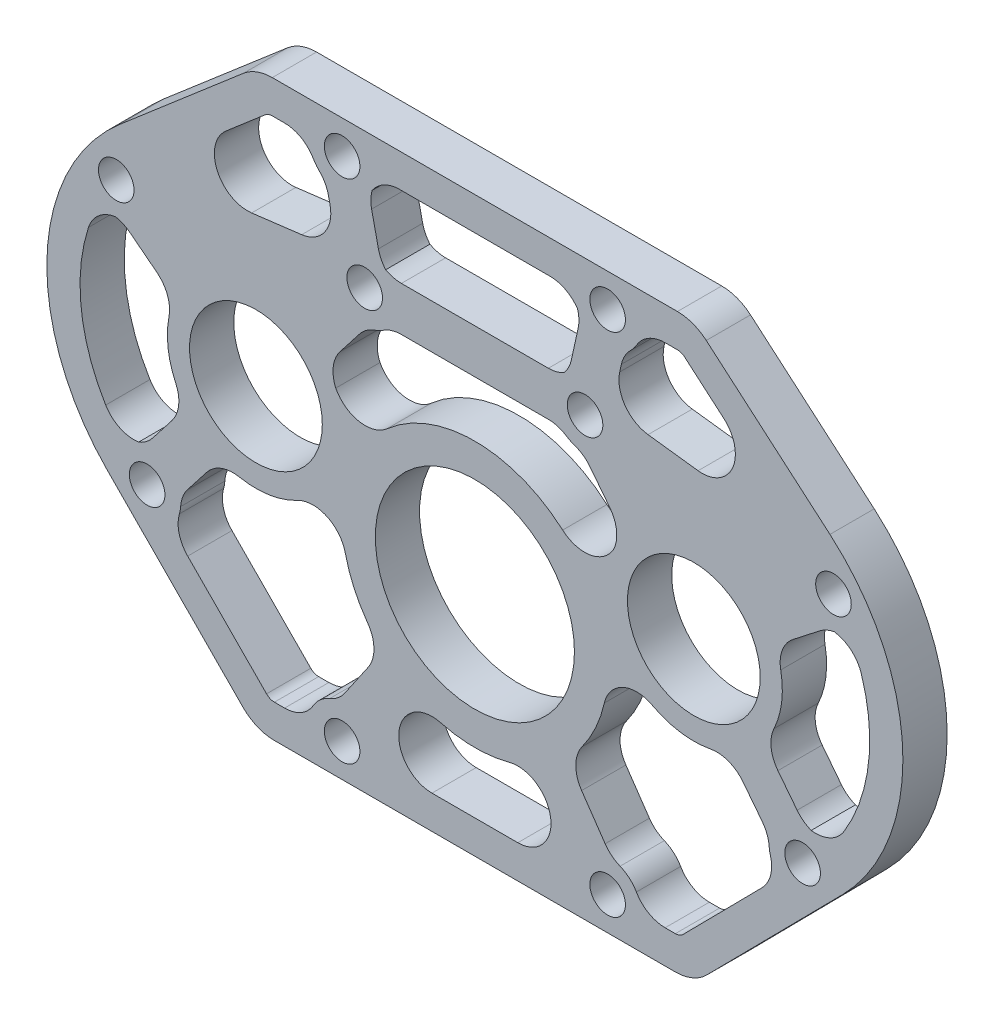
SolidWorks part; units mm, degrees
material "6061-T6 (SS)"
ref_plane "Front Plane" through (0, 0, 0) normal (0, 0, 1) x (1, 0, 0)
ref_plane "Top Plane" through (0, 0, 0) normal (0, 1, 0) x (1, 0, 0)
ref_plane "Right Plane" through (0, 0, 0) normal (1, 0, 0) x (0, 0, -1)
sketch "Sketch1" plane through (0, 0, 0) normal (0, 0, 1) x (1, 0, 0)
  line L0 (127, 25.4) -> (127, 0) construction
  line L1 (0, 0) -> (254, 0)
  line L2 (0, 0) -> (0, 25.4)
  line L3 (0, 25.4) -> (254, 25.4)
  line L4 (254, 0) -> (254, 25.4)
  line L18 (110.6338, 19.05) -> (106.9677, 12.7)
  line L19 (106.9677, 12.7) -> (110.6338, 6.35)
  line L20 (110.6338, 6.35) -> (117.9662, 6.35)
  line L21 (117.9662, 6.35) -> (121.6323, 12.7)
  line L22 (121.6323, 12.7) -> (117.9662, 19.05)
  line L23 (117.9662, 19.05) -> (110.6338, 19.05)
  circle A0 centre (82.8819, 22.86) radius 30 construction
  circle A1 centre (145.7181, 22.86) radius 30 construction
  circle A2 centre (82.8819, 22.86) radius 7.62 construction
  circle A3 centre (145.7181, 22.86) radius 8.636
  circle A4 centre (82.8819, 22.86) radius 8.636
  circle A5 centre (145.7181, 22.86) radius 7.62 construction
  circle A6 centre (114.3, 12.7) radius 25.4 construction
  circle A7 centre (114.3, 12.7) radius 26.67
  circle A8 centre (114.3, 12.7) radius 22.2377 construction
  circle A11 centre (114.3, 12.7) radius 6.35 construction
  dimension "D4" = 17.272
  dimension "D9" = 53.34
  dimension "D13" = 12.7
  dimension "D1" = 25.4
  dimension "D2" = 254
  dimension "D10" = 12.7
  dimension "D12" = 12.7
  dimension "D14" = 10.16
sketch "Sketch3" plane through (0, 0, 0) normal (0, 0, 1) x (1, 0, 0)
  line L0 (82.8819, 52.86) -> (145.7181, 52.86) construction
  line L5 (82.8819, -7.14) -> (145.7181, -7.14) construction
  line L6 (82.8819, 22.86) -> (98.4918, 42.8972) construction
  line L9 (114.3, 52.86) -> (114.3, -19.84) construction
  line L10 (63.3497, 45.6304) -> (82.8819, 62.385)
  line L25 (82.8819, 62.385) -> (145.7181, 62.385)
  line L26 (145.7181, 62.385) -> (165.2503, 45.6304)
  line L27 (110.6338, 19.05) -> (106.9677, 12.7)
  line L28 (106.9677, 12.7) -> (110.6338, 6.35)
  line L29 (110.6338, 6.35) -> (117.9662, 6.35)
  line L30 (117.9662, 6.35) -> (121.6323, 12.7)
  line L31 (121.6323, 12.7) -> (117.9662, 19.05)
  line L32 (117.9662, 19.05) -> (110.6338, 19.05)
  line L33 (110.565, 18.9308) -> (106.9677, 12.7)
  line L34 (106.9677, 12.7) -> (110.6338, 6.35)
  line L35 (110.6338, 6.35) -> (117.9662, 6.35)
  line L36 (117.9662, 6.35) -> (121.6323, 12.7)
  line L37 (121.6323, 12.7) -> (117.9662, 19.05)
  line L38 (117.9662, 19.05) -> (110.6338, 19.05)
  line L39 (96.3395, 30.6605) -> (132.2605, -5.2605) construction
  line L40 (82.8819, 22.86) -> (114.3, 12.7) construction
  line L41 (95.25, 57.6225) -> (133.35, 57.6225) construction
  line L43 (95.25, -15.0775) -> (133.35, -15.0775) construction
  line L44 (145.7181, -19.84) -> (167.0663, 1.7827)
  line L45 (82.8819, -19.84) -> (145.7181, -19.84)
  line L46 (61.5337, 1.7827) -> (82.8819, -19.84)
  line L47 (82.8819, 22.86) -> (67.272, 2.8228) construction
  line L48 (82.8819, 22.86) -> (67.272, 2.8228) construction
  line L49 (82.8819, 22.86) -> (62.8447, 38.4699) construction
  circle A2 centre (82.8819, 22.86) radius 30 construction
  circle A9 centre (114.3, 12.7) radius 26.67
  circle A10 centre (114.3, 12.7) radius 26.67 construction
  circle A11 centre (82.8819, 22.86) radius 8.636
  circle A12 centre (82.8819, 22.86) radius 8.636 construction
  circle A13 centre (145.7181, 22.86) radius 8.636
  circle A16 centre (145.7181, 22.86) radius 8.636 construction
  circle A17 centre (95.25, 57.6225) radius 2.5527
  circle A19 centre (114.3, 12.7) radius 25.4 construction
  circle A20 centre (114.3, 12.7) radius 22.2377 construction
  circle A22 centre (114.3, 12.7) radius 25.4 construction
  circle A23 centre (114.3, 12.7) radius 22.2377 construction
  arc A24 (112.6104, 26.8872) -> (104.6233, 2.1884) centre (82.8819, 22.86) ccw
  circle A25 centre (114.3, 12.7) radius 14.2875
  circle A26 centre (82.8819, 22.86) radius 9.525
  circle A27 centre (145.7181, 22.86) radius 9.525
  circle A37 centre (133.35, 57.6225) radius 2.5527
  circle A38 centre (133.35, -15.0775) radius 2.5527
  circle A39 centre (95.25, -15.0775) radius 2.5527
  circle A40 centre (67.272, 2.8228) radius 2.5527
  circle A41 centre (62.8447, 38.4699) radius 2.5527
  circle A42 centre (98.4918, 42.8972) radius 2.5527
  circle A43 centre (161.328, 2.8228) radius 2.5527
  circle A44 centre (165.7553, 38.4699) radius 2.5527
  circle A45 centre (130.1082, 42.8972) radius 2.5527
  circle A46 centre (95.25, -15.0775) radius 4.7625 construction
  arc A47 (123.9767, 2.1884) -> (115.9896, 26.8872) centre (145.7181, 22.86) ccw
  circle A48 centre (133.35, -15.0775) radius 4.7625 construction
  circle A49 centre (95.25, 57.6225) radius 4.7625 construction
  circle A50 centre (133.35, 57.6225) radius 4.7625 construction
  point P2 (114.3, 52.86)
  point P31 (114.3, -19.84)
  point P41 (114.3, 62.385)
  point P59 (114.3, 57.6225)
  point P60 (114.3, -15.0775)
  point P69 (114.3, 12.7)
  point P78 (82.8819, 22.86)
  point P84 (114.3, -22.0625)
  dimension "D3" = 70
  dimension "D4" = 9.525
  dimension "D2" = 45
  dimension "D8" = 25.4
  dimension "D14" = 28.575
  dimension "D15" = 19.05
  dimension "D16" = 3
  dimension "D5" = 5.1054
  dimension "D12" = 5.1054
  dimension "D7" = 4.7625
  dimension "D17" = 90
  dimension "2" = 50.8
  dimension "D6" = 19.05
  dimension "D18" = 7.9375
  dimension "D9" = 0
  dimension "D10" = 0
  dimension "D11" = 0
  dimension "D13" = 0
extrude "Boss-Extrude1" add sketch "Sketch3" along normal blind 6.35 contours A24 A10 L26 L25 L10 A37 A17 | A24 L46 L45 L44 A10 A38 A39 | A10 A24 A12 A40 A42 | A23 A24 A25 | A23 A22 A12 | A22 A24 A10 A12 | A22 A12 A10 A24 | A24 A22 A23 | A24 A10 A22 | A22 A24 A23 | A25 A24 A23 | A25 A23 A24 | A24 A23 A22 | A24 A22 A10 | A23 A24 A22 | A23 A45 A25 A44 | A22 A45 A23 A44 A16 | A23 A45 A22 | A22 A45 A16 A10 | A10 A16 A43 | A22 A44 A23 | A22 A44 A10 A16 | A10 A26 A12 | A22 A12 A10 | A12 A22 | A10 A27 A16 | A16 A22 | A22 A16 A10 region at (87.3231, 51.7029, 0) region at (114.3, 53.784, 0) region at (76.6658, -7.5892, 0) region at (98.4388, 17.8292, 0) region at (114.3, 34.3639, 0) region at (114.3, -6.358, 0) region at (141.2769, 51.7029, 0) region at (130.1612, 17.8292, 0)
fillet "Fillet1" radius 6.35 4 edges at (145.7181, -19.84, 3.175) (82.8819, -19.84, 3.175) (145.7181, 62.385, 3.175) (82.8819, 62.385, 3.175)
sketch "Sketch4" plane through (0, 0, 6.35) normal (0, 0, 1) x (1, 0, 0)
  line L0 (85.536, -15.0775) -> (143.064, -15.0775)
  line L1 (144.1937, -14.6053) -> (163.6773, 5.1287)
  line L2 (162.1496, 42.0156) -> (144.4013, 57.2399)
  line L3 (143.3677, 57.6225) -> (85.2323, 57.6225)
  line L4 (84.1987, 57.2399) -> (66.4504, 42.0156)
  line L5 (64.9227, 5.1287) -> (84.4063, -14.6053)
  line L6 (85.536, -19.84) -> (143.064, -19.84)
  line L7 (147.5827, -17.9514) -> (167.0663, 1.7827)
  line L8 (165.2503, 45.6304) -> (147.502, 60.8547)
  line L9 (143.3677, 62.385) -> (85.2323, 62.385)
  line L10 (81.098, 60.8547) -> (63.3497, 45.6304)
  line L11 (61.5337, 1.7827) -> (81.0173, -17.9514)
  line L12 (85.536, -19.84) -> (143.064, -19.84)
  line L13 (147.5827, -17.9514) -> (167.0663, 1.7827)
  line L14 (165.2503, 45.6304) -> (147.502, 60.8547)
  line L15 (143.3677, 62.385) -> (85.2323, 62.385)
  line L16 (81.098, 60.8547) -> (63.3497, 45.6304)
  line L17 (61.5337, 1.7827) -> (81.0173, -17.9514)
  line L18 (95.25, 57.6225) -> (98.4918, 42.8972) construction
  line L19 (98.4918, 42.8972) -> (130.1082, 42.8972) construction
  line L20 (130.1082, 42.8972) -> (133.35, 57.6225) construction
  line L21 (82.8819, 22.86) -> (114.3, 12.7) construction
  line L22 (114.3, 12.7) -> (95.25, -15.0775) construction
  line L23 (62.8447, 38.4699) -> (82.8819, 22.86) construction
  line L24 (82.8819, 22.86) -> (67.272, 2.8228) construction
  line L25 (165.7553, 38.4699) -> (145.7181, 22.86) construction
  line L26 (145.7181, 22.86) -> (161.328, 2.8228) construction
  line L27 (114.3, 12.7) -> (133.35, -15.0775) construction
  line L28 (114.3, 12.7) -> (145.7181, 22.86) construction
  line L29 (98.4918, 42.8972) -> (82.8819, 22.86) construction
  line L30 (130.1082, 42.8972) -> (145.7181, 22.86) construction
  line L31 (62.8447, 38.4699) -> (98.4918, 42.8972) construction
  line L32 (130.1082, 42.8972) -> (165.7553, 38.4699) construction
  line L33 (129.7168, 39.7464) -> (157.7573, 36.2639)
  line L34 (157.7573, 36.2639) -> (143.7668, 25.3647)
  line L35 (92.1493, 56.9399) -> (95.3911, 42.2146)
  line L36 (133.2089, 42.2146) -> (136.4507, 56.9399)
  line L37 (98.4918, 39.7222) -> (130.1082, 39.7222)
  line L38 (95.9872, 44.8485) -> (80.3773, 24.8112)
  line L39 (70.8427, 36.2639) -> (84.8332, 25.3647)
  line L40 (70.8427, 36.2639) -> (98.8832, 39.7464)
  line L41 (80.3773, 24.8112) -> (64.7674, 4.774)
  line L42 (81.905, 19.839) -> (113.3231, 9.679)
  line L43 (111.6816, 14.4957) -> (92.6316, -13.2818)
  line L44 (115.2769, 9.679) -> (146.695, 19.839)
  line L45 (111.6816, 10.9043) -> (130.7316, -16.8732)
  line L46 (143.2134, 20.9088) -> (158.8233, 0.8715)
  line L47 (127.6035, 40.946) -> (143.2134, 20.9088)
  line L48 (130.4995, 46.048) -> (169.4513, 41.2103)
  line L49 (171.2024, 38.6887) -> (147.6693, 20.3553)
  line L50 (98.3507, 58.3051) -> (101.5926, 43.5799)
  line L51 (127.0074, 43.5799) -> (130.2493, 58.3051)
  line L52 (98.4918, 46.0722) -> (130.1082, 46.0722)
  line L53 (100.9965, 40.946) -> (85.3866, 20.9088)
  line L54 (57.3976, 38.6887) -> (80.9307, 20.3553)
  line L55 (59.1487, 41.2103) -> (98.1005, 46.048)
  line L56 (85.3866, 20.9088) -> (69.7767, 0.8715)
  line L57 (83.8589, 25.881) -> (115.2769, 15.721)
  line L58 (116.9184, 10.9043) -> (97.8684, -16.8732)
  line L59 (113.3231, 15.721) -> (144.7411, 25.881)
  line L60 (116.9184, 14.4957) -> (135.9684, -13.2818)
  line L61 (148.2227, 24.8112) -> (163.8326, 4.774)
  line L62 (132.6128, 44.8485) -> (148.2227, 24.8112)
  line L63 (54.8467, 40.676) -> (98.1005, 46.048) construction
  line L64 (54.8467, 40.676) -> (80.9307, 20.3553) construction
  line L65 (130.4995, 46.048) -> (173.7533, 40.676) construction
  line L66 (173.7533, 40.676) -> (147.6693, 20.3553) construction
  arc A0 (143.064, -15.0775) -> (144.1937, -14.6053) centre (143.064, -13.49) ccw
  arc A1 (163.6773, 5.1287) -> (162.1496, 42.0156) centre (145.7181, 22.86) ccw
  arc A2 (144.4013, 57.2399) -> (143.3677, 57.6225) centre (143.3677, 56.035) ccw
  arc A3 (85.2323, 57.6225) -> (84.1987, 57.2399) centre (85.2323, 56.035) ccw
  arc A4 (66.4504, 42.0156) -> (64.9227, 5.1287) centre (82.8819, 22.86) ccw
  arc A5 (84.4063, -14.6053) -> (85.536, -15.0775) centre (85.536, -13.49) ccw
  arc A6 (143.064, -19.84) -> (147.5827, -17.9514) centre (143.064, -13.49) ccw
  arc A7 (167.0663, 1.7827) -> (165.2503, 45.6304) centre (145.7181, 22.86) ccw
  arc A8 (147.502, 60.8547) -> (143.3677, 62.385) centre (143.3677, 56.035) ccw
  arc A9 (85.2323, 62.385) -> (81.098, 60.8547) centre (85.2323, 56.035) ccw
  arc A10 (63.3497, 45.6304) -> (61.5337, 1.7827) centre (82.8819, 22.86) ccw
  arc A11 (81.0173, -17.9514) -> (85.536, -19.84) centre (85.536, -13.49) ccw
  arc A12 (143.064, -19.84) -> (147.5827, -17.9514) centre (143.064, -13.49) ccw
  arc A13 (167.0663, 1.7827) -> (165.2503, 45.6304) centre (145.7181, 22.86) ccw
  arc A14 (147.502, 60.8547) -> (143.3677, 62.385) centre (143.3677, 56.035) ccw
  arc A15 (85.2323, 62.385) -> (81.098, 60.8547) centre (85.2323, 56.035) ccw
  arc A16 (63.3497, 45.6304) -> (61.5337, 1.7827) centre (82.8819, 22.86) ccw
  arc A17 (81.0173, -17.9514) -> (85.536, -19.84) centre (85.536, -13.49) ccw
  circle A18 centre (95.25, 57.6225) radius 4.7625
  circle A19 centre (133.35, 57.6225) radius 4.7625
  circle A20 centre (95.25, -15.0775) radius 4.7625
  circle A21 centre (133.35, -15.0775) radius 4.7625
  circle A22 centre (161.328, 2.8228) radius 4.8142
  circle A23 centre (67.272, 2.8228) radius 4.8142
  circle A24 centre (62.8447, 38.4699) radius 4.6
  circle A25 centre (165.7553, 38.4699) radius 4.6
  circle A26 centre (98.4918, 42.8972) radius 4.7625
  circle A27 centre (130.1082, 42.8972) radius 4.7625
  circle A28 centre (114.3, 12.7) radius 19.05
  circle A29 centre (82.8819, 22.86) radius 12.7
  circle A30 centre (145.7181, 22.86) radius 12.7
  dimension "D3" = 38.1
  dimension "D4" = 25.4
  dimension "D5" = 3.175
  dimension "D1" = 0
  dimension "D2" = 4.7625
  dimension "D6" = 3.175
extrude "Cut-Extrude1" cut sketch "Sketch4" against normal up to surface (6.35 mm away) contours A29 L54 A24 A4 A23 L41 | A26 L35 A18 L3 A3 L4 L55 | A27 L51 A19 L3 A18 L50 A26 L52 | A27 L48 L2 A2 L3 A19 L36 | A30 L61 A22 A1 A25 L49 | A30 L44 A28 L60 A21 L0 A0 L1 A22 L46 | A28 L58 A20 L0 A21 L45 | A29 L56 A23 L5 A5 L0 A20 L43 A28 L42 | A30 L47 A27 L37 A26 L53 A29 L57 A28 L59 region at (142.3086, -0.1956, 6.35) region at (114.3, -10.7853, 6.35) region at (86.2914, -0.1956, 6.35) region at (164.1431, 20.6053, 6.35) region at (114.3, 32.9152, 6.35) region at (64.4569, 20.6053, 6.35) region at (145.2048, 49.2972, 6.35) region at (114.3, 51.9634, 6.35) region at (83.3952, 49.2972, 6.35) up to face at (114.3, 22.1956, 0)
fillet "Fillet2" radius 4.7625 50 edges at (66.5888, 42.1343, 3.175) (92.9125, 53.4731, 3.175) (90.4875, 57.6225, 3.175) (72.8202, 15.1108, 3.175) (66.9913, 7.6288, 3.175) (63.8856, 6.2446, 3.175) (60.4965, 34.5144, 3.175) (63.5193, 33.9196, 3.175) (71.2302, 27.9125, 3.175) (128.5875, -15.0775, 3.175) (100.0125, -15.0775, 3.175) (106.2948, -4.5864, 3.175) (122.3052, -4.5864, 3.175) (101.058, -0.995, 3.175) (94.6393, -10.3543, 3.175) (90.4875, -15.0775, 3.175) (70.6174, -0.6391, 3.175) (72.0006, 3.7263, 3.175) (77.8295, 11.2083, 3.175) (150.7705, 11.2083, 3.175) (157.9826, -0.6391, 3.175) (138.1125, -15.0775, 3.175) (133.9607, -10.3543, 3.175) (127.542, -0.995, 3.175) (156.5994, 3.7263, 3.175) (157.3698, 27.9125, 3.175) (165.0807, 33.9196, 3.175) (164.7144, 6.2446, 3.175) (161.6087, 7.6288, 3.175) (155.7798, 15.1108, 3.175) (168.1035, 34.5144, 3.175) (126.5584, 46.0722, 3.175) (102.0416, 46.0722, 3.175) (100.8294, 47.0466, 3.175) (99.114, 54.8384, 3.175) (100.0125, 57.6225, 3.175) (129.486, 54.8384, 3.175) (127.7706, 47.0466, 3.175) (128.5875, 57.6225, 3.175) (135.6875, 53.4731, 3.175) (138.1125, 57.6225, 3.175) (162.0112, 42.1343, 3.175) (135.6563, 30.6092, 3.175) (92.9437, 30.6092, 3.175) (102.0416, 39.7222, 3.175) (126.5584, 39.7222, 3.175) (129.785, 38.1457, 3.175) (98.815, 38.1457, 3.175) (95.559, 22.0974, 3.175) (133.041, 22.0974, 3.175)
sketch "Sketch6" plane through (0, 0, 0) normal (0, 0, -1) x (-1, 0, 0)
  line L1 (-94.5778, 45.6105) -> (-89.4535, 44.9741)
  line L2 (-95.4508, 15.4586) -> (-93.6052, 16.0554) construction
  line L3 (-134.9948, 16.0554) -> (-133.1492, 15.4586) construction
  line L4 (-95.4508, 15.4586) -> (-93.6052, 16.0554)
  line L5 (-134.9948, 16.0554) -> (-133.1492, 15.4586)
  line L6 (-125.6419, -15.0775) -> (-102.9581, -15.0775) construction
  line L9 (-120.4591, -15.0775) -> (-125.6419, -15.0775)
  line L10 (-128.7239, -13.9458) -> (-124.3867, -7.6214)
  line L12 (-135.3187, 51.7979) -> (-133.9721, 45.6813) construction
  line L13 (-146.3291, 44.082) -> (-134.0222, 45.6105) construction
  line L14 (-94.5778, 45.6105) -> (-82.2709, 44.082) construction
  line L15 (-94.6279, 45.6813) -> (-93.2813, 51.7979) construction
  line L18 (-135.0823, 50.7242) -> (-133.9721, 45.6813)
  line L19 (-139.1465, 44.9741) -> (-134.0222, 45.6105)
  line L21 (-94.6279, 45.6813) -> (-93.5177, 50.7242)
  line L28 (-114.3, 62.385) -> (-114.3, -19.84) construction
  line L29 (-85.2323, 62.385) -> (-143.3677, 62.385) construction
  line L30 (-85.536, -19.84) -> (-143.064, -19.84) construction
  line L31 (-99.8761, -13.9458) -> (-104.2208, -7.6106) construction
  line L37 (-99.8761, -13.9458) -> (-104.2133, -7.6214)
  line L38 (-108.1409, -15.0775) -> (-102.9581, -15.0775)
  arc A6 (-94.3879, 28.2361) -> (-95.4485, 24.6959) centre (-82.8819, 22.86) ccw construction
  arc A7 (-94.5778, 45.6105) -> (-94.6279, 45.6813) centre (-98.4918, 42.8972) ccw construction
  arc A12 (-133.9721, 45.6813) -> (-134.0222, 45.6105) centre (-130.1082, 42.8972) ccw construction
  arc A13 (-94.5778, 45.6105) -> (-94.6279, 45.6813) centre (-98.4918, 42.8972) ccw
  arc A14 (-133.9721, 45.6813) -> (-134.0222, 45.6105) centre (-130.1082, 42.8972) ccw
  arc A15 (-139.7588, 11.6449) -> (-132.8793, 8.4914) centre (-137.5241, 7.4393) cw
  arc A16 (-148.1162, 10.3885) -> (-134.9948, 16.0554) centre (-145.7181, 22.86) ccw construction
  arc A17 (-133.1492, 15.4586) -> (-129.6949, 1.4795) centre (-114.3, 12.7) ccw construction
  arc A18 (-95.7207, 8.4914) -> (-88.8412, 11.6449) centre (-91.0759, 7.4393) cw
  arc A19 (-98.9051, 1.4795) -> (-95.4508, 15.4586) centre (-114.3, 12.7) ccw construction
  arc A20 (-93.6052, 16.0554) -> (-80.4838, 10.3885) centre (-82.8819, 22.86) ccw construction
  arc A21 (-93.6052, 16.0554) -> (-88.8412, 11.6449) centre (-82.8819, 22.86) ccw
  arc A22 (-95.7207, 8.4914) -> (-95.4508, 15.4586) centre (-114.3, 12.7) ccw
  arc A23 (-133.1492, 15.4586) -> (-132.8793, 8.4914) centre (-114.3, 12.7) ccw
  arc A24 (-139.7588, 11.6449) -> (-134.9948, 16.0554) centre (-145.7181, 22.86) ccw
  arc A26 (-101.7029, 26.9904) -> (-94.2795, 28.4622) centre (-98.5536, 30.563) ccw
  arc A27 (-126.8971, 26.9904) -> (-131.1954, 21.5005) centre (-114.3, 12.7) ccw
  arc A32 (-135.0823, 50.7242) -> (-139.1465, 44.9741) centre (-139.7335, 49.7003) cw
  arc A33 (-93.5177, 50.7242) -> (-89.4535, 44.9741) centre (-88.8665, 49.7003) ccw
  arc A34 (-97.4046, 21.5005) -> (-95.4485, 24.6959) centre (-100.161, 25.3843) ccw construction
  arc A35 (-97.4046, 21.5005) -> (-131.1954, 21.5005) centre (-114.3, 12.7) ccw construction
  arc A36 (-133.1515, 24.6959) -> (-131.1954, 21.5005) centre (-128.439, 25.3843) ccw construction
  arc A37 (-133.1515, 24.6959) -> (-134.2121, 28.2361) centre (-145.7181, 22.86) ccw construction
  arc A38 (-94.2795, 28.4622) -> (-95.4485, 24.6959) centre (-82.8819, 22.86) ccw
  arc A39 (-97.4046, 21.5005) -> (-95.4485, 24.6959) centre (-100.161, 25.3843) ccw
  arc A40 (-97.4046, 21.5005) -> (-101.7029, 26.9904) centre (-114.3, 12.7) ccw
  arc A41 (-133.1515, 24.6959) -> (-131.1954, 21.5005) centre (-128.439, 25.3843) ccw
  arc A42 (-133.1515, 24.6959) -> (-134.3205, 28.4622) centre (-145.7181, 22.86) ccw
  arc A43 (-134.3205, 28.4622) -> (-126.8971, 26.9904) centre (-130.0464, 30.563) ccw
  arc A55 (-125.6419, -15.0775) -> (-128.7239, -13.9458) centre (-125.6419, -10.315) cw
  arc A58 (-102.9581, -15.0775) -> (-99.8761, -13.9458) centre (-102.9581, -10.315) ccw construction
  arc A59 (-102.9581, -15.0775) -> (-99.8761, -13.9458) centre (-102.9581, -10.315) ccw
  arc A60 (-104.2133, -7.6214) -> (-108.1409, -15.0775) centre (-108.1409, -10.315) cw
  arc A61 (-124.3867, -7.6214) -> (-120.4591, -15.0775) centre (-120.4591, -10.315) ccw
  point P20 (-109.629, -15.1928)
  point P65 (-102.9581, -15.0775)
  point P67 (-108.1256, -15.0775)
  dimension "D1" = 4.7625
extrude "Boss-Extrude2" add sketch "Sketch6" against normal up to surface (6.35 mm away) contours A61 L10 A55 L9 | L37 A60 L38 A59 | L5 A23 A15 A24 | A41 A27 A43 A42 | A39 A38 A26 A40 | L4 A21 A18 A22 | L21 A33 L1 A13 | L18 A14 L19 A32 region at (125.7627, -13.0807, 0) up to face at (114.3, 22.1956, 6.35)
equation "\"NEO\"= 60mm"
equation "\"D3@Sketch1\"=\"NEO\""
equation "\"D5@Sketch1\"=\"NEO\""
